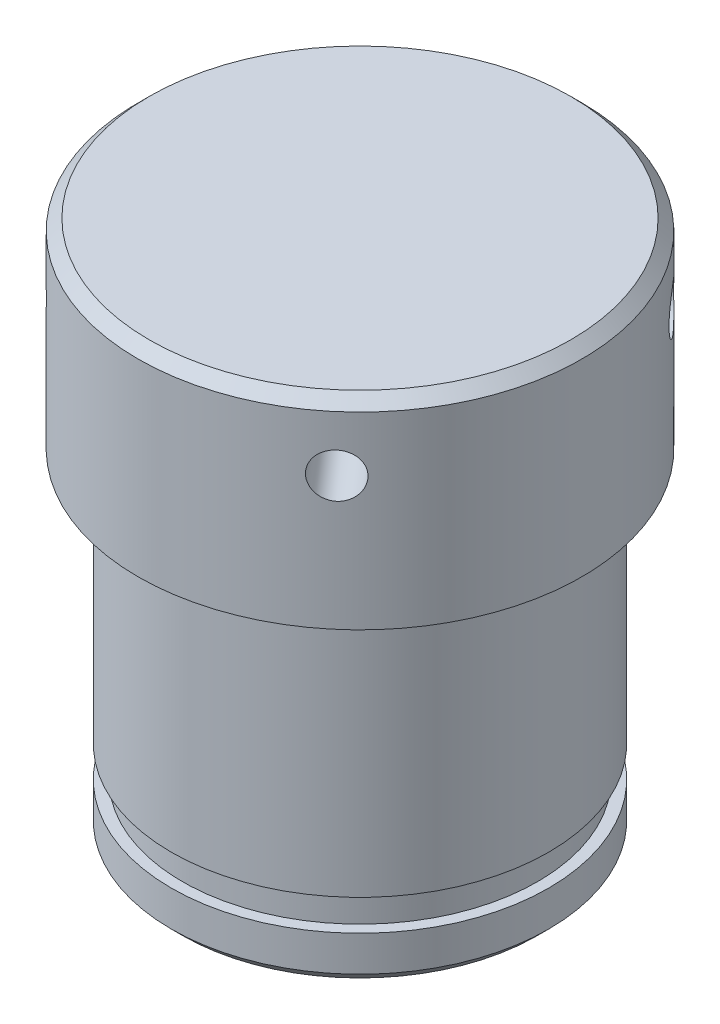
SolidWorks part; units mm, degrees
material "ABS"
ref_plane "Спереди" through (0, 0, 0) normal (0, 0, 1) x (1, 0, 0)
ref_plane "Сверху" through (0, 0, 0) normal (0, 1, 0) x (1, 0, 0)
ref_plane "Справа" through (0, 0, 0) normal (1, 0, 0) x (0, 0, -1)
sketch "Эскиз1" plane through (0, 0, 0) normal (0, 1, 0) x (1, 0, 0)
  circle A0 centre (0, 0) radius 8.5
  dimension "D1" = 17
extrude "Бобышка-Вытянуть1" add sketch "Эскиз1" along normal blind 15
sketch "Эскиз2" plane through (0, 15, 0) normal (0, 1, 0) x (1, 0, 0)
  circle A0 centre (0, 0) radius 10
  dimension "D1" = 20
extrude "Бобышка-Вытянуть2" add sketch "Эскиз2" along normal blind 9
sketch "Эскиз3" plane through (0, 0, 0) normal (0, -1, 0) x (1, 0, 0)
  circle A0 centre (0, 6) radius 1
  circle A1 centre (6, 0) radius 1
  circle A2 centre (0, -6) radius 1
  circle A3 centre (-6, 0) radius 1
  point P12 (0, 0)
  dimension "D1" = 2
  dimension "D2" = 6
  dimension "D3" = 4
extrude "Вырез-Вытянуть1" cut sketch "Эскиз3" against normal blind 10
sketch "Эскиз4" plane through (0, 0, 0) normal (0, -1, 0) x (1, 0, 0)
  circle A0 centre (0, 0) radius 8
  circle A1 centre (0, 0) radius 8.5
  dimension "D1" = 16
extrude "Вырез-Вытянуть2" cut sketch "Эскиз4" against normal blind 1.4 from offset 2.1 offset against normal yes
chamfer "Фаска1" distance 0.5 angle 45 2 edges at (0, 0, 8.5) (0, 24, 10)
sketch "Эскиз6" plane through (0, 24, 0) normal (0, 1, 0) x (1, 0, 0)
  line L0 (0, 12.2337) -> (0, -13.1957) construction
ref_plane "Плоскость1" through (6.5246, 0, 7.5782) normal (0.6525, 0, 0.7578) x (0.7578, 0, -0.6525)
sketch "Эскиз7" plane through (6.5246, 0, 7.5782) normal (0.6525, 0, 0.7578) x (0.7578, 0, -0.6525)
  line L0 (7.982, 24) -> (-8.6096, 24) construction
  circle A0 centre (0, 21) radius 1
  dimension "D1" = 2
  dimension "D2" = 3
extrude "Вырез-Вытянуть3" cut sketch "Эскиз7" against normal blind 8
pattern_circular "Круговой массив1" count 4 over 360 about axis through (0, 24, 0) along (0, -1, 0) of "Вырез-Вытянуть3"
